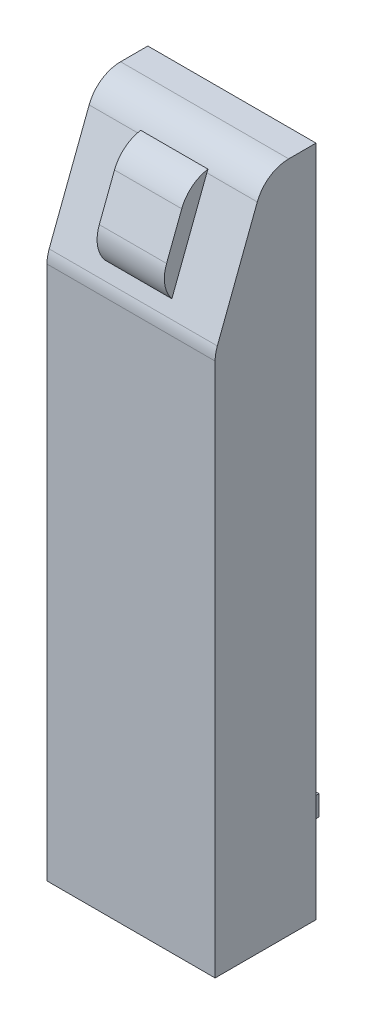
SolidWorks part; units mm, degrees
ref_plane "Alzado" through (0, 0, 0) normal (0, 0, 1) x (1, 0, 0)
ref_plane "Planta" through (0, 0, 0) normal (0, 1, 0) x (1, 0, 0)
ref_plane "Vista lateral" through (0, 0, 0) normal (1, 0, 0) x (0, 0, -1)
sketch "Croquis1" plane through (0, 0, 0) normal (0, 0, 1) x (1, 0, 0)
  line L1 (25, -100) -> (-25, -100)
  line L2 (25, -100) -> (25, 100)
  line L3 (25, 100) -> (-25, 100)
  line L4 (-25, -100) -> (-25, 100)
  line L5 (25, -100) -> (-25, 100) construction
  line L6 (25, 100) -> (-25, -100) construction
  point P0 (0, 0)
  dimension "D1" = 200
  dimension "D2" = 50
extrude "Saliente-Extruir1" add sketch "Croquis1" along normal blind 30
sketch "Croquis2" plane through (-25, 0, 0) normal (-1, 0, 0) x (0, 0, 1)
  line L1 (30, 100) -> (0, 100) construction
  line L2 (15, 100) -> (30, 60.7065)
  line L4 (30, 100) -> (30, -100) construction
  line L5 (15, 100) -> (30, 100)
  line L6 (30, 100) -> (30, 60.7065)
extrude "Cortar-Extruir1" cut sketch "Croquis2" against normal blind 60
sketch "Croquis3" plane through (0, 17.717, 46.4109) normal (0, 0.3566, 0.9342) x (1, 0, 0)
  line L2 (10, 52.045) -> (-10, 52.045)
  line L3 (10, 52.045) -> (10, 82.045)
  line L12 (10, 82.045) -> (-10, 82.045)
  line L13 (-10, 52.045) -> (-10, 82.045)
  point P2 (0, 67.045)
  dimension "D2" = 30
  dimension "D3" = 20
extrude "Saliente-Extruir2" add sketch "Croquis3" along normal blind 5
fillet "Redondeo1" radius 10 2 edges at (0, 60.7065, 30) (0, 100, 15)
fillet "Redondeo2" radius 10 2 edges at (0, 68.1228, 32.5208) (0, 96.1501, 21.8216)
sketch "Croquis5" plane through (0, 0, 0) normal (0, 0, -1) x (-1, 0, 0)
  line L0 (0, 0) -> (0, -4)
  line L1 (-2.5, 72.5) -> (-10, 72.5)
  line L2 (0, 60) -> (-2.5, 60)
  line L4 (0, 80) -> (-2.5, 80)
  line L5 (-2.5, 60) -> (-2.5, 67.5)
  line L6 (0, 80) -> (2.5, 80)
  line L8 (0, 60) -> (2.5, 60)
  line L9 (2.5, 80) -> (2.5, 72.5)
  line L10 (10, 67.5) -> (2.5, 67.5)
  line L11 (10, 67.5) -> (10, 72.5)
  line L12 (10, 72.5) -> (2.5, 72.5)
  line L13 (-10, 67.5) -> (-10, 72.5)
  line L15 (-20.9086, -72.0722) -> (-14.9086, -72.0722)
  line L16 (-2.5, 72.5) -> (-2.5, 80)
  line L17 (-2.5, 69.375) -> (-2.5, 70.625)
  line L18 (-2.5, 67.5) -> (-10, 67.5)
  line L19 (2.5, 69.375) -> (2.5, 60)
  line L20 (-20.9086, -72.0722) -> (-20.9086, -78.0722)
  line L22 (-20.9086, -78.0722) -> (-14.9086, -78.0722)
  line L25 (-14.9086, -72.0722) -> (-14.9086, -78.0722)
  line L28 (-14.9086, -72.0722) -> (-14.9086, -78.0722)
  line L29 (21.0914, -78.0722) -> (15.0914, -78.0722)
  line L30 (21.0914, -78.0722) -> (21.0914, -72.0722)
  line L32 (-20.9086, -78.0722) -> (-20.9086, -72.0722)
  line L34 (-8.9086, -72.0722) -> (-8.9086, -78.0722)
  line L35 (-8.9086, -72.0722) -> (-2.9086, -72.0722)
  line L36 (-8.9086, -72.0722) -> (-8.9086, -78.0722)
  line L37 (-8.9086, -78.0722) -> (-2.9086, -78.0722)
  line L38 (-2.9086, -72.0722) -> (-2.9086, -78.0722)
  line L40 (-2.9086, -72.0722) -> (-2.9086, -78.0722)
  line L42 (3.0914, -72.0722) -> (3.0914, -78.0722)
  line L43 (3.0914, -72.0722) -> (9.0914, -72.0722)
  line L44 (3.0914, -72.0722) -> (3.0914, -78.0722)
  line L45 (3.0914, -78.0722) -> (9.0914, -78.0722)
  line L46 (9.0914, -72.0722) -> (9.0914, -78.0722)
  line L48 (9.0914, -72.0722) -> (9.0914, -78.0722)
  line L50 (15.0914, -72.0722) -> (15.0914, -78.0722)
  line L51 (15.0914, -72.0722) -> (21.0914, -72.0722)
  line L52 (15.0914, -72.0722) -> (15.0914, -78.0722)
  line L53 (15.0914, -78.0722) -> (21.0914, -78.0722)
  line L54 (21.0914, -72.0722) -> (21.0914, -78.0722)
  line L55 (-14.9086, -78.0722) -> (-20.9086, -78.0722)
  line L56 (-2.9086, -78.0722) -> (-8.9086, -78.0722)
  line L58 (9.0914, -78.0722) -> (3.0914, -78.0722)
  circle A0 centre (0, 26) radius 8
  circle A1 centre (0, 0) radius 4
  circle A2 centre (-12.5, 0) radius 4
  circle A3 centre (12.5, 0) radius 4
  circle A4 centre (0, -50) radius 4
  circle A6 centre (0, -62.5) radius 4
  point P8 (0, 70)
  dimension "D7" = 16
  dimension "D1" = 8
  dimension "D8" = 8
  dimension "D9" = 8
  dimension "D10" = 8
  dimension "D11" = 6
  dimension "D12" = 8
  dimension "D2" = 20
  dimension "D3" = 2.5
  dimension "D4" = 2.5
  dimension "D5" = 20
  dimension "D6" = 5
  dimension "D13" = 42
  dimension "D14" = 6
  dimension "D15" = 6
  dimension "D16" = 6
  dimension "D17" = 6
  dimension "D18" = 6
  dimension "D19" = 6
extrude "Saliente-Extruir3" add sketch "Croquis5" along normal blind 5 contours L19 L10 L11 L12 L9 L6 L4 L16 L1 L13 L18 L5 L2 L8 | A0 | A2 | A4 | A6 | L25 L15 L20 L22 | L38 L35 L34 L37 | L46 L43 L42 L45 | L51 L50 L29 L30 | A1 | A3 region at (0, 70, 0) region at (17.9086, -75.0722, 0) region at (-18.0914, -75.0722, 0) region at (5.9086, -75.0722, 0) region at (-6.0914, -75.0722, 0) region at (0, 26, 0) region at (12.5, 0, 0) region at (0, -50, 0) region at (0, -62.5, 0)
